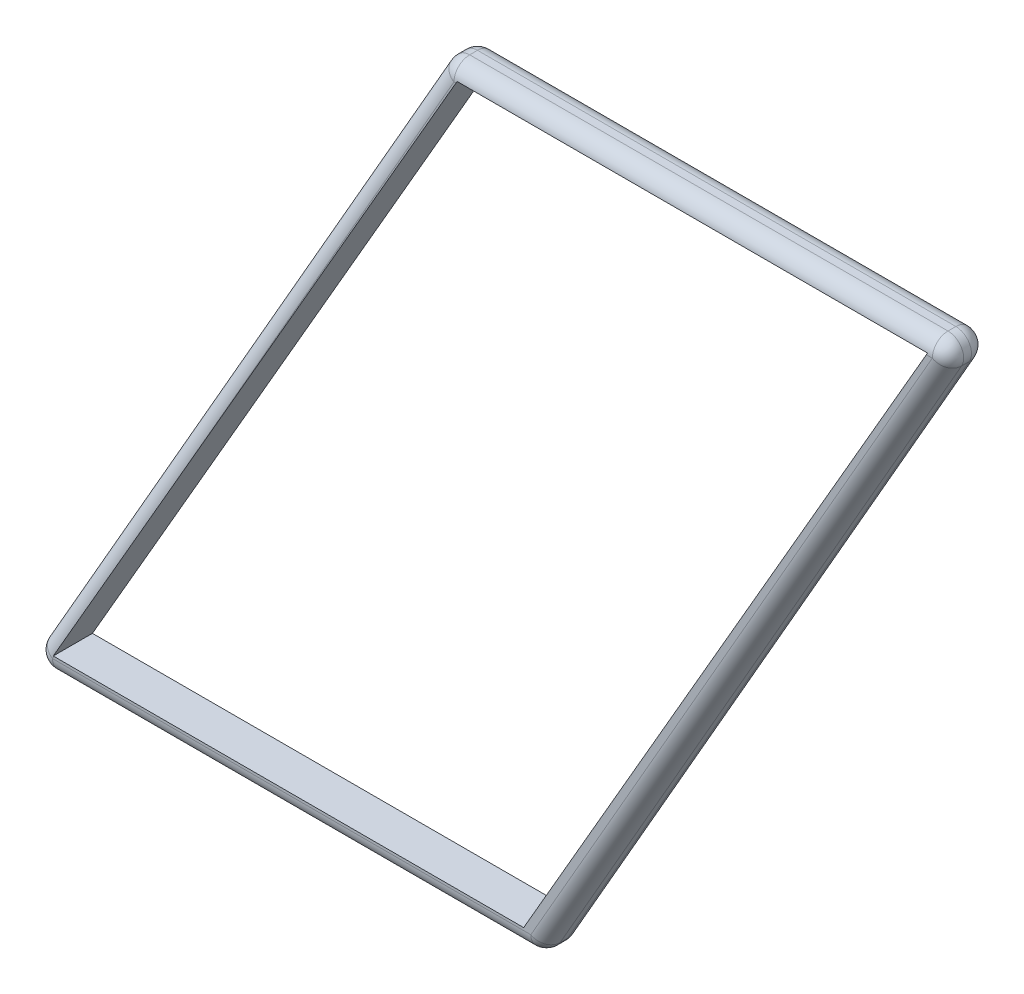
SolidWorks part; units mm, degrees
ref_plane "Front Plane" through (0, 0, 0) normal (0, 0, 1) x (1, 0, 0)
ref_plane "Top Plane" through (0, 0, 0) normal (0, 1, 0) x (1, 0, 0)
ref_plane "Right Plane" through (0, 0, 0) normal (1, 0, 0) x (0, 0, -1)
sketch "Sketch1" plane through (0, 0, 0) normal (0, 0, 1) x (1, 0, 0)
  line L1 (-0.0425, 0.446) -> (0.5575, 0.446)
  line L2 (-0.0425, 0.446) -> (-0.5575, -0.446)
  line L3 (-0.5575, -0.446) -> (0.0425, -0.446)
  line L4 (0.5575, 0.446) -> (0.0425, -0.446)
  line L5 (-0.0425, 0.446) -> (0.0425, -0.446) construction
  line L6 (-0.5575, -0.446) -> (0.5575, 0.446) construction
  point P0 (0, 0)
  point P5 (0, 0)
  point P6 (7.62, 20.3481)
  point P8 (0, 0)
  dimension "D1" = 1.03
  dimension "D2" = 0.6
  dimension "D3" = 60
sketch "Sketch2" plane through (0, 0, 0) normal (0, 0, 1) x (1, 0, 0)
  line L0 (-0.593, -0.4693) -> (0.0632, -0.4693)
  line L1 (-0.593, -0.4693) -> (-0.058, 0.4636)
  line L2 (0.0632, -0.4693) -> (0.5982, 0.4636)
  line L3 (-0.058, 0.4636) -> (0.5982, 0.4636)
  point P0 (0.5982, 0.4636)
extrude "Boss-Extrude1" add sketch "Sketch2" along normal mid plane 0.05
extrude "Cut-Extrude2" cut sketch "Sketch1" against normal mid plane 0.05
fillet "Fillet4" radius 0.02 2 edges at (0.2701, 0.4636, -0.025) (0.2701, 0.4636, 0.025)
fillet "Fillet5" radius 0.02 5 edges at (0.325, -0.0129, 0.025) (0.5949, 0.4577, 0.0191) (0.5982, 0.4636, 0) (0.5949, 0.4577, -0.0191) (0.325, -0.0129, -0.025)
fillet "Fillet6" radius 0.02 5 edges at (-0.3312, -0.0129, 0.025) (-0.0613, 0.4577, 0.0191) (-0.058, 0.4636, 0) (-0.0613, 0.4577, -0.0191) (-0.3312, -0.0129, -0.025)
fillet "Fillet7" radius 0.02 8 edges at (-0.5862, -0.4693, -0.0191) (-0.593, -0.4693, 0) (-0.5862, -0.4693, 0.0191) (-0.2649, -0.4693, 0.025) (0.0565, -0.4693, 0.0191) (0.0632, -0.4693, 0) (0.0565, -0.4693, -0.0191) (-0.2649, -0.4693, -0.025)
